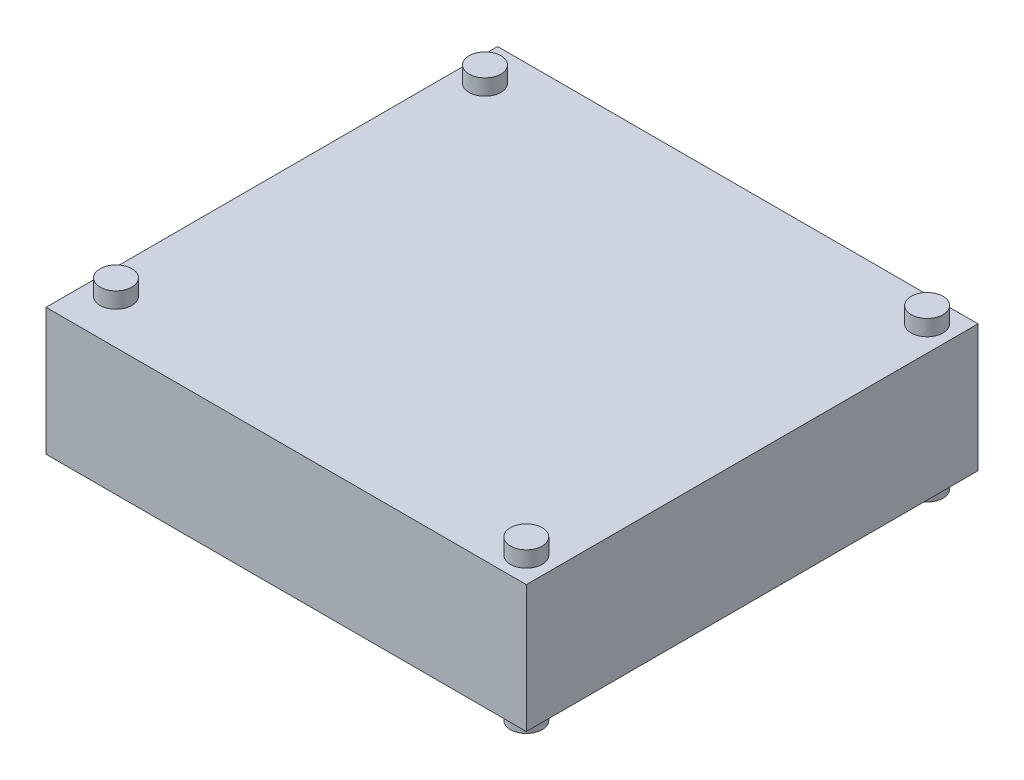
SolidWorks part; units mm, degrees
ref_plane "Front" through (0, 0, 0) normal (0, 0, 1) x (1, 0, 0)
ref_plane "Top" through (0, 0, 0) normal (0, 1, 0) x (1, 0, 0)
ref_plane "Right" through (0, 0, 0) normal (1, 0, 0) x (0, 0, -1)
sketch "Sketch1" plane through (0, 0, 0) normal (0, 1, 0) x (1, 0, 0)
  line L1 (-47.9425, 45.085) -> (47.9425, 45.085)
  line L2 (-47.9425, 45.085) -> (-47.9425, -45.085)
  line L3 (-47.9425, -45.085) -> (47.9425, -45.085)
  line L4 (47.9425, 45.085) -> (47.9425, -45.085)
  line L5 (-47.9425, 45.085) -> (47.9425, -45.085) construction
  line L6 (-47.9425, -45.085) -> (47.9425, 45.085) construction
  circle A0 centre (-42.8625, 37.465) radius 3.175
  circle A1 centre (-42.8625, -36.195) radius 3.175
  circle A2 centre (42.8625, 40.005) radius 3.175
  circle A3 centre (42.8625, -40.005) radius 3.175
  point P0 (0, 0)
  dimension "D3" = 6.35
  dimension "D4" = 5.08
  dimension "D5" = 5.08
  dimension "D6" = 5.08
  dimension "D7" = 8.89
  dimension "D8" = 5.08
  dimension "D9" = 5.08
  dimension "D10" = 7.62
  dimension "D11" = 5.08
  dimension "D1" = 95.885
  dimension "D2" = 90.17
extrude "Boss-Extrude1" add sketch "Sketch1" along normal blind 25.4
extrude "Boss-Extrude2" add sketch "Sketch1<2>" along normal blind 28.575 and the other way blind 3.175 contours A1 | A0 | A2 | A3 region at (-42.8625, 0, 36.195)
sketch "Sketch1<2>" plane through (0, 0, 0) normal (0, 1, 0) x (1, 0, 0) same geometry as "Sketch1"
